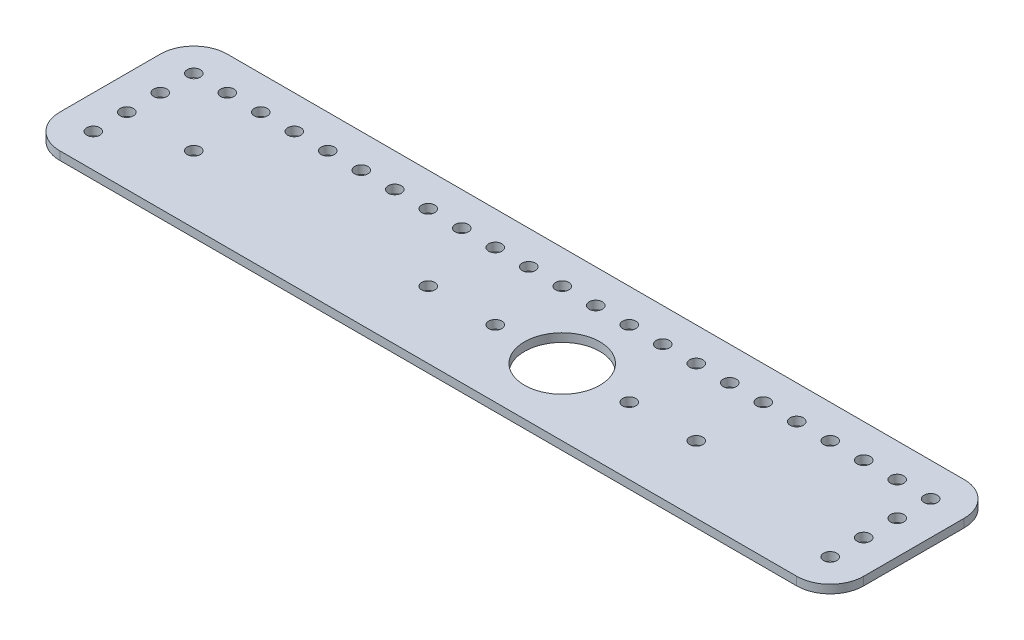
SolidWorks part; units mm, degrees
material "6061 Alloy"
ref_plane "Front Plane" through (0, 0, 0) normal (0, 0, 1) x (1, 0, 0)
ref_plane "Top Plane" through (0, 0, 0) normal (0, 1, 0) x (1, 0, 0)
ref_plane "Right Plane" through (0, 0, 0) normal (1, 0, 0) x (0, 0, -1)
sketch "Sketch1" plane through (0, 0, 0) normal (0, 1, 0) x (1, 0, 0)
  line L0 (0, 0) -> (0, 63.5)
  line L1 (0, 63.5) -> (304.8, 63.5)
  line L2 (304.8, 63.5) -> (304.8, 0)
  line L3 (304.8, 0) -> (279.4, 0)
  line L4 (279.4, 0) -> (279.4, 38.1)
  line L5 (279.4, 38.1) -> (25.4, 38.1)
  line L6 (25.4, 38.1) -> (25.4, 0)
  line L7 (25.4, 0) -> (0, 0)
  line L8 (12.7, 50.8) -> (25.4, 50.8) construction
  line L9 (12.7, 50.8) -> (12.7, 38.1) construction
  line L10 (25.4, 0) -> (279.4, 0)
  circle A0 centre (12.7, 50.8) radius 2.4892
  circle A1 centre (25.4, 50.8) radius 2.4892
  circle A2 centre (38.1, 50.8) radius 2.4892
  circle A3 centre (50.8, 50.8) radius 2.4892
  circle A4 centre (63.5, 50.8) radius 2.4892
  circle A5 centre (76.2, 50.8) radius 2.4892
  circle A6 centre (88.9, 50.8) radius 2.4892
  circle A7 centre (101.6, 50.8) radius 2.4892
  circle A8 centre (114.3, 50.8) radius 2.4892
  circle A9 centre (127, 50.8) radius 2.4892
  circle A10 centre (139.7, 50.8) radius 2.4892
  circle A11 centre (152.4, 50.8) radius 2.4892
  circle A12 centre (165.1, 50.8) radius 2.4892
  circle A13 centre (177.8, 50.8) radius 2.4892
  circle A14 centre (190.5, 50.8) radius 2.4892
  circle A15 centre (203.2, 50.8) radius 2.4892
  circle A16 centre (215.9, 50.8) radius 2.4892
  circle A17 centre (228.6, 50.8) radius 2.4892
  circle A18 centre (241.3, 50.8) radius 2.4892
  circle A19 centre (254, 50.8) radius 2.4892
  circle A20 centre (266.7, 50.8) radius 2.4892
  circle A21 centre (279.4, 50.8) radius 2.4892
  circle A22 centre (292.1, 50.8) radius 2.4892
  circle A23 centre (12.7, 38.1) radius 2.4892
  circle A24 centre (292.1, 38.1) radius 2.4892
  circle A25 centre (12.7, 25.4) radius 2.4892
  circle A26 centre (292.1, 25.4) radius 2.4892
  circle A27 centre (12.7, 12.7) radius 2.4892
  circle A28 centre (292.1, 12.7) radius 2.4892
  dimension "D6" = 12.7
  dimension "D7" = 12.7
  dimension "D8" = 4.9784
  dimension "D1" = 25.4
  dimension "D2" = 304.8
  dimension "D3" = 25.4
  dimension "D4" = 25.4
  dimension "D5" = 63.5
  dimension "D10" = 12.7
  dimension "D12" = 12.7
  dimension "D9" = 23
  dimension "D11" = 4
extrude "Boss-Extrude1" add sketch "Sketch1" along normal blind 3.175 contours L6 L10 L4 L5 | L7 L6 L5 L4 L3 L2 L1 L0 A28 A27 A26 A25 A24 A23 A22 A21 A20 A19 A18 A17 A16 A15 A14 region at (152.4, 0, -44.3822) region at (152.4, 0, -19.05)
sketch "Sketch2" plane through (0, 3.175, 0) normal (0, 1, 0) x (1, 0, 0)
  line B0 (68.7873, 5.0409) -> (202.7488, 5.0409)
  line B1 (202.7488, 74.8909) -> (68.7873, 74.8909)
  circle B2 centre (237.8973, 39.9659) radius 2.54
  circle B3 centre (221.6286, 39.9659) radius 2.54
  arc B4 (216.9621, 58.6686) -> (222.2457, 55.8409) centre (222.2457, 62.1909) ccw
  arc B5 (68.7873, 74.8909) -> (63.5038, 72.0633) centre (68.7873, 68.5409) ccw
  arc B6 (47.3973, 62.1909) -> (41.0473, 55.8409) centre (47.3973, 55.8409) ccw
  circle B7 centre (187.0973, 39.9659) radius 14.2875
  circle B8 centre (152.5659, 39.9659) radius 2.54
  circle B9 centre (107.7223, 62.1909) radius 2.4892
  circle B10 centre (136.2973, 39.9659) radius 2.54
  circle B11 centre (107.7223, 17.7409) radius 2.4892
  circle B12 centre (69.6223, 17.7409) radius 2.4892
  circle B13 centre (47.3973, 39.9659) radius 2.54
  circle B14 centre (69.6223, 62.1909) radius 2.4892
sketch_block_instance "Block-new elevator gusset-1"
sketch_block "Block-new elevator gusset"
sketch "Sketch3" plane through (0, 3.175, 0) normal (0, 1, 0) x (1, 0, 0)
  line L0 (304.8, 63.5) -> (304.8, 0) construction
  line L2 (0, 63.5) -> (304.8, 63.5) construction
  circle A0 centre (60.3142, 47.625) radius 2.4892 construction
  circle A1 centre (98.4142, 47.625) radius 2.4892 construction
  circle A2 centre (126.9892, 25.4) radius 2.4892
  circle A3 centre (143.2579, 25.4) radius 2.4892 construction
  circle A4 centre (177.7892, 25.4) radius 14.2875
  circle A5 centre (212.3206, 25.4) radius 2.4892 construction
  circle A6 centre (228.5892, 25.4) radius 2.4892
  circle A7 centre (98.4142, 3.175) radius 2.4892 construction
  circle A8 centre (60.3142, 3.175) radius 2.4892 construction
  circle A9 centre (38.0892, 25.4) radius 2.4892
  circle A10 centre (152.3892, 25.4) radius 2.4892
  circle A11 centre (203.1892, 25.4) radius 2.4892
  point P22 (0, 0)
  dimension "D1" = 28.575
  dimension "D2" = 4.9784
  dimension "D3" = 44.45
  dimension "D4" = 38.1
  dimension "D5" = 22.225
  dimension "D6" = 16.2686
  dimension "D7" = 16.2686
  dimension "D8" = 34.5314
  dimension "D9" = 34.5314
  dimension "D10" = 28.575
  dimension "D11" = 22.225
  dimension "D12" = 127.0108
  dimension "D13" = 38.1
  dimension "D14" = 25.4
  dimension "D15" = 25.4
extrude "Cut-Extrude1" cut sketch "Sketch3" against normal through all
fillet "Fillet1" radius 12.7 4 edges at (0, 1.5875, -63.5) (304.8, 1.5875, -63.5) (304.8, 1.5875, 0) (0, 1.5875, 0)
sketch "Sketch4" plane through (0, 3.175, 0) normal (0, -1, 0) x (1, 0, 0)
  line L0 (-1033.1809, 0) -> (48966.8191, 0) construction
  line L1 (0, -968.3084) -> (0, 49031.6916) construction
  point P3 (0, 0)
  point P5 (-55.2439, 31.6916)
  point P6 (0, 0)
